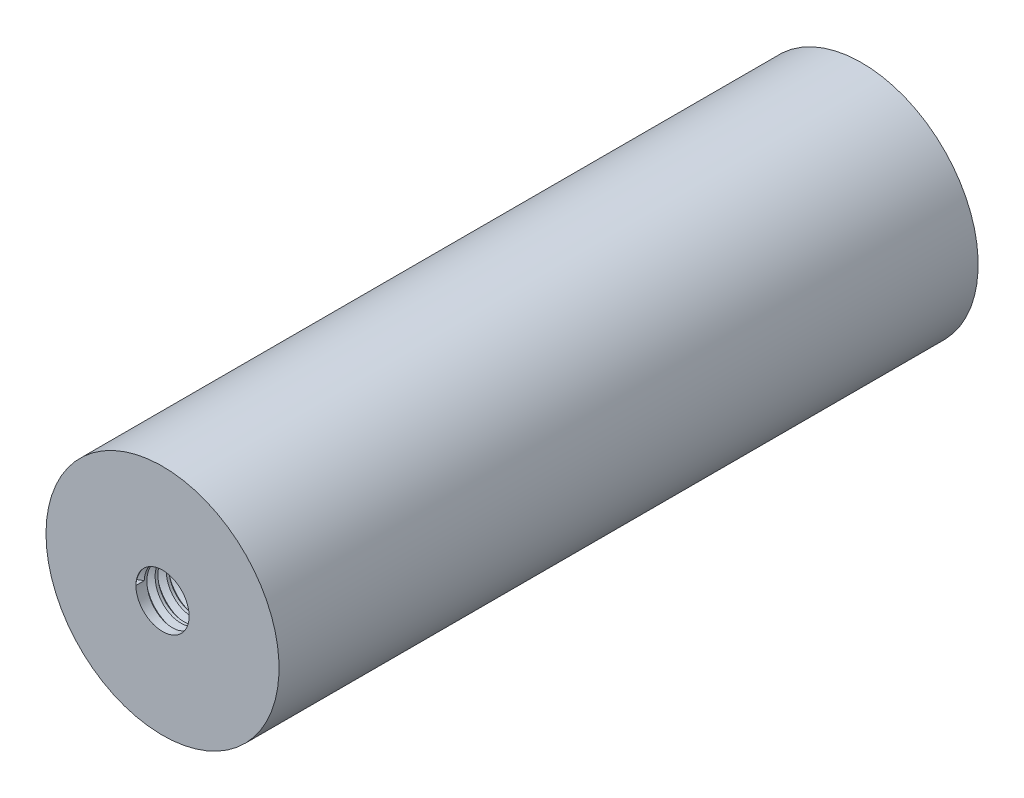
SolidWorks part; units mm, degrees
material "Stainless Steel (ferritic)"
ref_plane "Front Plane" through (0, 0, 0) normal (0, 0, 1) x (1, 0, 0)
ref_plane "Top Plane" through (0, 0, 0) normal (0, 1, 0) x (1, 0, 0)
ref_plane "Right Plane" through (0, 0, 0) normal (1, 0, 0) x (0, 0, -1)
sketch "Sketch1" plane through (0, 0, 0) normal (0, 0, 1) x (1, 0, 0)
  circle A0 centre (0, 0) radius 6.35
  dimension "D1" = 12.7
extrude "Boss-Extrude1" add sketch "Sketch1" along normal blind 38.1
hole_wizard "Tap Drill for M3.5 Tap2" positions "Sketch6" profile "Sketch7" hole size "M3.5" standard "ISO"
sketch "Sketch6" plane through (0, 0, 38.1) normal (0, 0, 1) x (1, 0, 0)
  point P0 (0, 0)
sketch "Sketch7" plane through (0, 0, 38.1) normal (1, 0, 0) x (0, -1, 0)
  line L0 (0, 0) -> (0, 12.8712)
  line L1 (0, 12.8712) -> (1.45, 12)
  line L2 (1.45, 12) -> (1.45, 0)
  line L5 (1.45, 0) -> (0, 0)
  line L10 (0, 12.8712) -> (-1.45, 12) construction
  line L11 (0, -6.35) -> (0, 107.95) construction
  dimension "Hole Dia." = 2.9
  dimension "Hole Depth" = 12
  dimension "Drill Angle" = 118
thread "Thread1" pitch 0.6 method cut profile "Thread Profile1" start angle 0, offset 0, length 10, pitch 0.6, diameter 2.9
ref_plane "Plane1" through (-1.45, 0, 38.1) normal (0, -1, 0) x (-1, 0, 0)
sketch "Thread Profile1" plane through (-1.45, 0, 38.1) normal (0, -1, 0) x (-1, 0, 0)
  line L0 (0, 0) -> (0, 0.6) construction
  line L1 (0, 0) -> (0.3248, 0.1875)
  line L2 (0.3248, 0.1875) -> (0.3248, 0.2625)
  line L3 (0.3248, 0.2625) -> (0, 0.45)
  line L4 (0.3248, 0.225) -> (0, 0.225) construction
  line L11 (0, 0) -> (0, 0.45)
  point P2 (0, 0)
  dimension "Pitch" = 0.6
  dimension "Profile_Angle" = 60
  dimension "Profile_Land" = 0.075
  dimension "Profile_Height" = 0.3248
